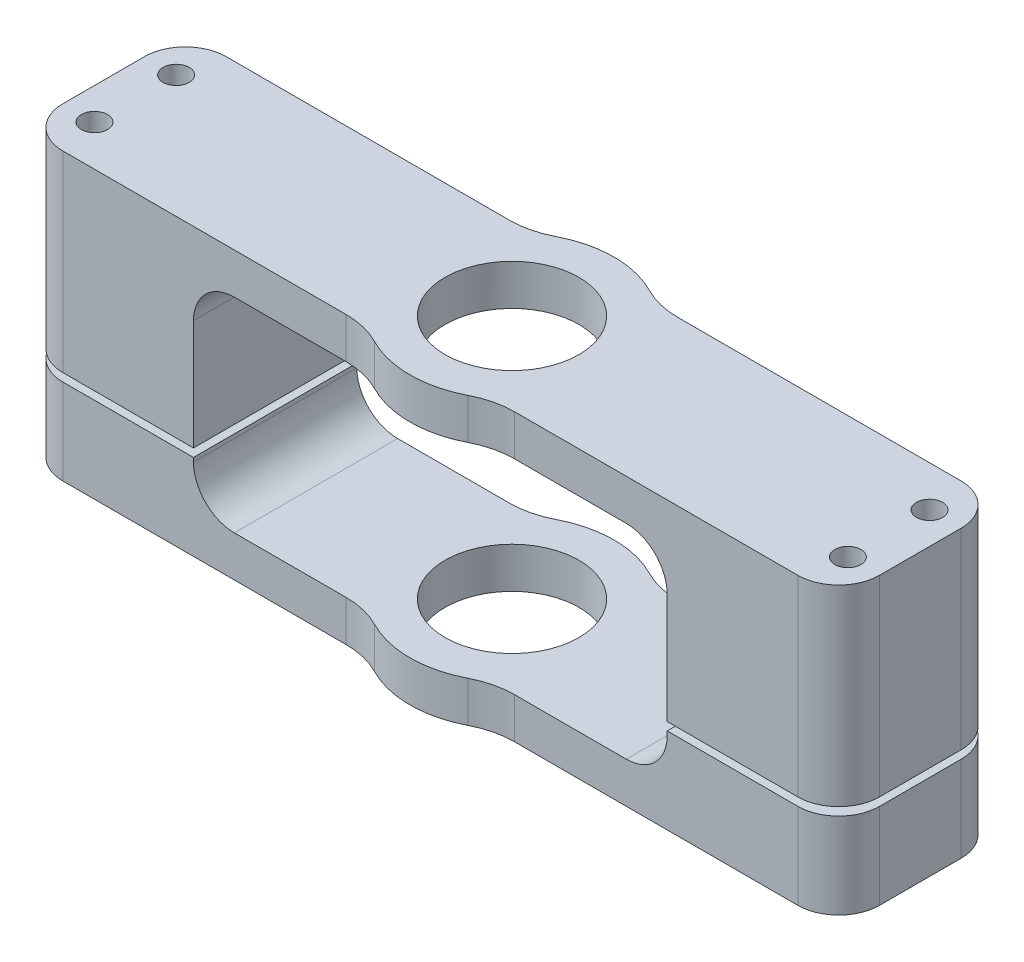
SolidWorks part; units mm, degrees
ref_plane "Front Plane" through (0, 0, 0) normal (0, 0, 1) x (1, 0, 0)
ref_plane "Top Plane" through (0, 0, 0) normal (0, 1, 0) x (1, 0, 0)
ref_plane "Right Plane" through (0, 0, 0) normal (1, 0, 0) x (0, 0, -1)
sketch "Sketch1" plane through (0, 0, 0) normal (0, 1, 0) x (1, 0, 0)
  line L0 (-44, 0) -> (-44, -44) construction
  line L1 (-44, -44) -> (44, -44) construction
  line L2 (44, -44) -> (44, 0) construction
  line L4 (-44, -10) -> (44, -10)
  line L5 (-44, -10) -> (-44, 10)
  line L6 (-44, 10) -> (44, 10)
  line L7 (44, -10) -> (44, 10)
  line L8 (-44, -10) -> (44, 10) construction
  line L9 (-44, 10) -> (44, -10) construction
  arc A0 (44, 0) -> (-44, 0) centre (0, 0) ccw construction
  dimension "D1" = 88
  dimension "D2" = 88
  dimension "D3" = 20
extrude "Boss-Extrude1" add sketch "Sketch1" along normal blind 35
sketch "Sketch2" plane through (0, 0, 10) normal (0, 0, 1) x (1, 0, 0)
  line L0 (-44, 0) -> (44, 0) construction
  line L1 (-1044, 11) -> (48956, 11) construction
  line L2 (0, -1000) -> (0, 49000) construction
  line L3 (-44, 35) -> (-44, 0) construction
  circle A0 centre (-38, 11) radius 4.25
  circle A1 centre (38, 11) radius 4.25
  point P2 (-44, 17.5)
  dimension "D1" = 8.5
  dimension "D2" = 6
  dimension "D3" = 11
extrude "Cut-Extrude1" cut sketch "Sketch2" against normal through all
sketch "Sketch7" plane through (0, 35, 0) normal (0, 1, 0) x (1, 0, 0)
  circle A0 centre (0, 0) radius 12.5
  dimension "D1" = 25
extrude "Boss-Extrude2" add sketch "Sketch7" against normal up to surface (35 mm away) up to face at (0, 0, 0)
sketch "Sketch4" plane through (0, 35, 0) normal (0, 1, 0) x (1, 0, 0)
  circle A0 centre (0, 0) radius 8.2
  dimension "D1" = 16.4
extrude "Cut-Extrude3" cut sketch "Sketch4" against normal through all
fillet "Fillet2" radius 10 4 edges at (7.5, 17.5, 10) (-7.5, 17.5, 10) (7.5, 17.5, -10) (-7.5, 17.5, -10)
sketch "Sketch10" plane through (0, 0, 0) normal (0, 0, 1) x (1, 0, 0)
  line L0 (44, 0) -> (10.3078, 0) construction
  line L1 (29, 30) -> (-29, 30)
  line L2 (29, 30) -> (29, 5)
  line L3 (29, 5) -> (-29, 5)
  line L4 (-29, 30) -> (-29, 5)
  line L6 (-44, 35) -> (-44, 0) construction
  line L7 (44, 35) -> (44, 0) construction
  line L8 (44, 35) -> (10.3078, 35) construction
  dimension "D1" = 5
  dimension "D2" = 15
  dimension "D3" = 15
  dimension "D4" = 5
extrude "Cut-Extrude5" cut sketch "Sketch10" against normal through all and the other way through all
fillet "Fillet3" radius 5 4 edges at (-29, 5, 0) (29, 5, 0) (-29, 30, 0) (29, 30, 0)
sketch "Sketch11" plane through (44, 0, 0) normal (1, 0, 0) x (0, 0, -1)
  line L4 (10, 0) -> (10, 35)
  line L5 (10, 35) -> (-10, 35)
  line L6 (-10, 35) -> (-10, 0)
  line L7 (-10, 0) -> (10, 0)
  line L8 (10, 0) -> (10, 35)
  line L10 (-10, 35) -> (-10, 0)
  line L11 (-10, 0) -> (10, 0)
  line L13 (10, 35) -> (-10, 35)
  dimension "D1" = 0
extrude "Boss-Extrude3" add sketch "Sketch11" along normal blind 6
sketch "Sketch12" plane through (0, 35, 0) normal (0, 1, 0) x (1, 0, 0)
  line L2 (50, 10) -> (10.3078, 10) construction
  line L3 (10.3078, -10) -> (50, -10) construction
  circle A0 centre (46.1249, 5) radius 1.6
  circle A1 centre (46.1249, -5) radius 1.6
  point P9 (0, 0)
  point P10 (0, 0)
  point P11 (0, 0)
  point P12 (0, 0)
  dimension "D1" = 3.2
  dimension "D2" = 5
  dimension "D3" = 5
extrude "Cut-Extrude6" cut sketch "Sketch12" against normal through all
mirror "Mirror1" about plane through (0, 0, 0) normal (1, 0, 0) of "Cut-Extrude6", "Boss-Extrude3"
fillet "Fillet5" radius 5 4 edges at (-50, 17.5, -10) (-50, 17.5, 10) (50, 17.5, 10) (50, 17.5, -10)
sketch "Sketch13" plane through (0, 0, 10) normal (0, 0, 1) x (1, 0, 0)
  circle A4 centre (38, 11) radius 4.25 construction
  circle A5 centre (38, 11) radius 4.25
  circle A6 centre (-38, 11) radius 4.25 construction
  circle A7 centre (-38, 11) radius 4.25
extrude "Boss-Extrude4" add sketch "Sketch13" against normal blind 4
sketch "Sketch14" plane through (0, 0, -10) normal (0, 0, -1) x (-1, 0, 0)
  line L1 (-50, 10.5) -> (50, 10.5)
  line L2 (-50, 10.5) -> (-50, 11.5)
  line L3 (-50, 11.5) -> (50, 11.5)
  line L4 (50, 10.5) -> (50, 11.5)
  line L5 (-50, 10.5) -> (50, 11.5) construction
  line L6 (-50, 11.5) -> (50, 10.5) construction
  line L7 (50, 35) -> (50, 0) construction
  point P0 (0, 11)
  point P8 (38, 11)
  dimension "D1" = 1
extrude "Cut-Extrude7" cut sketch "Sketch14" against normal through all
